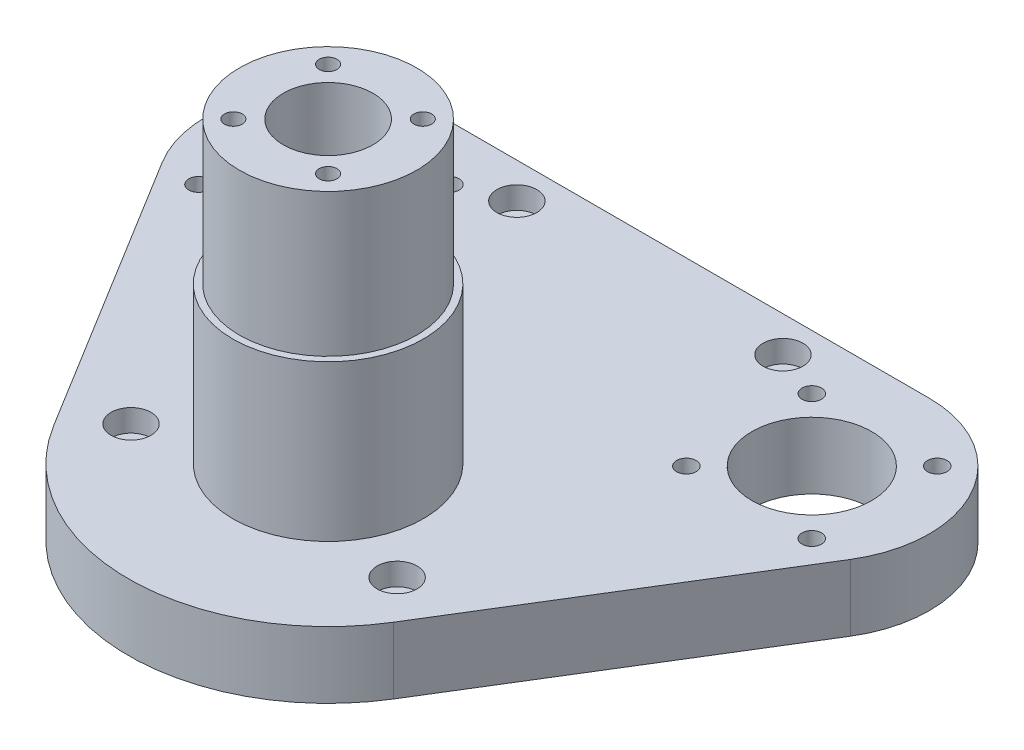
SolidWorks part; units mm, degrees
ref_plane "Front Plane" through (0, 0, 0) normal (0, 0, 1) x (1, 0, 0)
ref_plane "Top Plane" through (0, 0, 0) normal (0, 1, 0) x (1, 0, 0)
ref_plane "Right Plane" through (0, 0, 0) normal (1, 0, 0) x (0, 0, -1)
sketch "Sketch1" plane through (0, 0, 0) normal (0, 1, 0) x (1, 0, 0)
  line L0 (0, 0) -> (55, 54.0672) construction
  line L1 (55, 54.0672) -> (-55, 54.0672) construction
  line L2 (-55, 54.0672) -> (0, 0) construction
  line L3 (-77.5681, 40.1772) -> (-38.3231, -23.5868)
  line L4 (-55, 80.5672) -> (55, 80.5672)
  line L5 (38.3231, -23.5868) -> (77.5681, 40.1772)
  circle A0 centre (-55, 54.0672) radius 26.5 construction
  circle A1 centre (55, 54.0672) radius 26.5 construction
  circle A2 centre (0, 0) radius 45 construction
  arc A3 (-77.5681, 40.1772) -> (-55, 80.5672) centre (-55, 54.0672) cw
  arc A4 (55, 80.5672) -> (77.5681, 40.1772) centre (55, 54.0672) cw
  arc A5 (-38.3231, -23.5868) -> (38.3231, -23.5868) centre (0, 0) ccw
  dimension "D3" = 53
  dimension "D4" = 90
  dimension "D1" = 110
  dimension "D2" = 77.125
extrude "Main Body" add sketch "Sketch1" along normal blind 15 contours A5 L5 A4 L4 A3 L3
sketch "Sketch3" plane through (0, 15, 0) normal (0, 1, 0) x (1, 0, 0)
  circle A0 centre (0, 0) radius 45 construction
  circle A1 centre (0, 0) radius 45 construction
  circle A2 centre (0, 0) radius 21.5
  dimension "D1" = 43
extrude "Front Extrusion" add sketch "Sketch3" along normal blind 67.3
sketch "Sketch4" plane through (0, 0, 0) normal (0, -1, 0) x (1, 0, 0)
  line L0 (0, -1000) -> (0, 49000) construction
  line L1 (-45, 0) -> (45, 0) construction
  line L2 (-81.5, -54.0672) -> (-28.5, -54.0672) construction
  line L3 (55, -54.0672) -> (-55, -54.0672) construction
  line L4 (-55, -27.5672) -> (-55, -80.5672) construction
  line L5 (-10.6773, 10.6773) -> (0, 0) construction
  line L6 (-10.6773, -10.6773) -> (0, 0) construction
  line L7 (-69.1421, -39.9251) -> (-55, -54.0672) construction
  line L8 (-55, -80.5672) -> (55, -80.5672) construction
  line L10 (-30, -72.5672) -> (0, -72.5672) construction
  line L11 (-30, -72.5672) -> (-30, 14.4328) construction
  line L12 (-30, 14.4328) -> (0, 14.4328) construction
  line L13 (0, -72.5672) -> (0, 14.4328) construction
  circle A0 centre (55, -54.0672) radius 26.5 construction
  circle A1 centre (0, 0) radius 45 construction
  circle A2 centre (-55, -54.0672) radius 26.5 construction
  circle A3 centre (55, -54.0672) radius 26.5 construction
  circle A4 centre (0, 0) radius 45 construction
  circle A5 centre (-55, -54.0672) radius 26.5 construction
  circle A6 centre (0, 0) radius 10.1
  circle A7 centre (-55, -54.0672) radius 13.5
  circle A10 centre (-10.6773, 10.6773) radius 2
  arc A12 (-77.5681, -40.1772) -> (-55, -80.5672) centre (-55, -54.0672) ccw construction
  circle A13 centre (-10.6773, -10.6773) radius 2
  circle A14 centre (-69.1421, -39.9251) radius 2.2
  circle A15 centre (-69.1421, -68.2094) radius 2.2
  circle A16 centre (-40.8579, -68.2094) radius 2.2
  circle A17 centre (-40.8579, -39.9251) radius 2.2
  circle A18 centre (55, -54.0672) radius 13.5
  circle A19 centre (69.1421, -68.2094) radius 2.2
  circle A20 centre (40.8579, -68.2094) radius 2.2
  circle A21 centre (40.8579, -39.9251) radius 2.2
  circle A22 centre (69.1421, -39.9251) radius 2.2
  circle A23 centre (10.6773, -10.6773) radius 2
  circle A24 centre (10.6773, 10.6773) radius 2
  circle A25 centre (-30, -72.5672) radius 2.5
  circle A26 centre (-30, 14.4328) radius 2.5
  circle A27 centre (30, -72.5672) radius 2.5
  circle A28 centre (30, 14.4328) radius 2.5
  dimension "D1" = 20.2
  dimension "D2" = 27
  dimension "D4" = 4
  dimension "D5" = 45
  dimension "D7" = 4.4
  dimension "D9" = 5
  dimension "D3" = 15.1
  dimension "D6" = 20
  dimension "D8" = 45
  dimension "D10" = 30
  dimension "D11" = 8
  dimension "D12" = 87
extrude "Bolt Holes" cut sketch "Sketch4" against normal through all
sketch "Sketch5" plane through (0, 0, 0) normal (0, -1, 0) x (1, 0, 0)
  line L0 (-14.92, 6.4347) -> (-9.9876, 1.5024)
  line L1 (-6.4347, 14.92) -> (-1.5024, 9.9876)
  line L2 (-10.6773, 10.6773) -> (0, 0) construction
  line L3 (-1000, 0) -> (49000, 0) construction
  line L4 (0, -1000) -> (0, 49000) construction
  line L5 (-14.92, -6.4347) -> (-9.9876, -1.5024)
  line L6 (-6.4347, -14.92) -> (-1.5024, -9.9876)
  line L7 (6.4347, -14.92) -> (1.5024, -9.9876)
  line L8 (14.92, -6.4347) -> (9.9876, -1.5024)
  line L9 (14.92, 6.4347) -> (9.9876, 1.5024)
  line L10 (6.4347, 14.92) -> (1.5024, 9.9876)
  circle A0 centre (-10.6773, 10.6773) radius 2 construction
  circle A1 centre (-10.6773, 10.6773) radius 6 construction
  circle A2 centre (0, 0) radius 10.1 construction
  arc A3 (-14.92, 6.4347) -> (-6.4347, 14.92) centre (-10.6773, 10.6773) cw
  circle A4 centre (0, 0) radius 10.1 construction
  arc A5 (-9.9876, 1.5024) -> (-1.5024, 9.9876) centre (0, 0) cw
  arc A6 (-14.92, -6.4347) -> (-6.4347, -14.92) centre (-10.6773, -10.6773) ccw
  arc A7 (-9.9876, -1.5024) -> (-1.5024, -9.9876) centre (0, 0) ccw
  arc A8 (14.92, -6.4347) -> (6.4347, -14.92) centre (10.6773, -10.6773) cw
  arc A9 (9.9876, -1.5024) -> (1.5024, -9.9876) centre (0, 0) cw
  arc A10 (14.92, 6.4347) -> (6.4347, 14.92) centre (10.6773, 10.6773) ccw
  arc A11 (9.9876, 1.5024) -> (1.5024, 9.9876) centre (0, 0) ccw
  dimension "D1" = 4
  dimension "D2" = 4
extrude "Bolt Recesses Rear" cut sketch "Sketch5" against normal blind 5
sketch "Sketch6" plane through (0, 15, 0) normal (0, 1, 0) x (1, 0, 0)
  circle A1 centre (30, 72.5672) radius 4.5
  circle A2 centre (-30, -14.4328) radius 2.5 construction
  circle A3 centre (30, -14.4328) radius 2.5 construction
  circle A4 centre (30, 72.5672) radius 2.5 construction
  circle A5 centre (-30, 72.5672) radius 2.5 construction
  circle A6 centre (-30, -14.4328) radius 2.5 construction
  circle A7 centre (30, -14.4328) radius 2.5 construction
  circle A8 centre (30, 72.5672) radius 2.5 construction
  circle A9 centre (-30, 72.5672) radius 2.5 construction
  circle A10 centre (-30, 72.5672) radius 4.5
  circle A11 centre (-30, -14.4328) radius 4.5
  circle A12 centre (30, -14.4328) radius 4.5
  dimension "D1" = 9
extrude "Bolt Recesses Front" cut sketch "Sketch6" against normal blind 5
ref_plane "First Bearing Section" through (0, 50.1, 0) normal (0, 1, 0) x (1, 0, 0)
sketch "Sketch7" plane through (0, 82.3, 0) normal (0, 1, 0) x (1, 0, 0)
  circle A0 centre (0, 0) radius 21.5 construction
  circle A1 centre (0, 0) radius 21.5
  circle A2 centre (0, 0) radius 20
  dimension "D1" = 40
extrude "Cut-Extrude1" cut sketch "Sketch7" against normal up to surface (32.2 mm away) up to plane "First Bearing Section"
